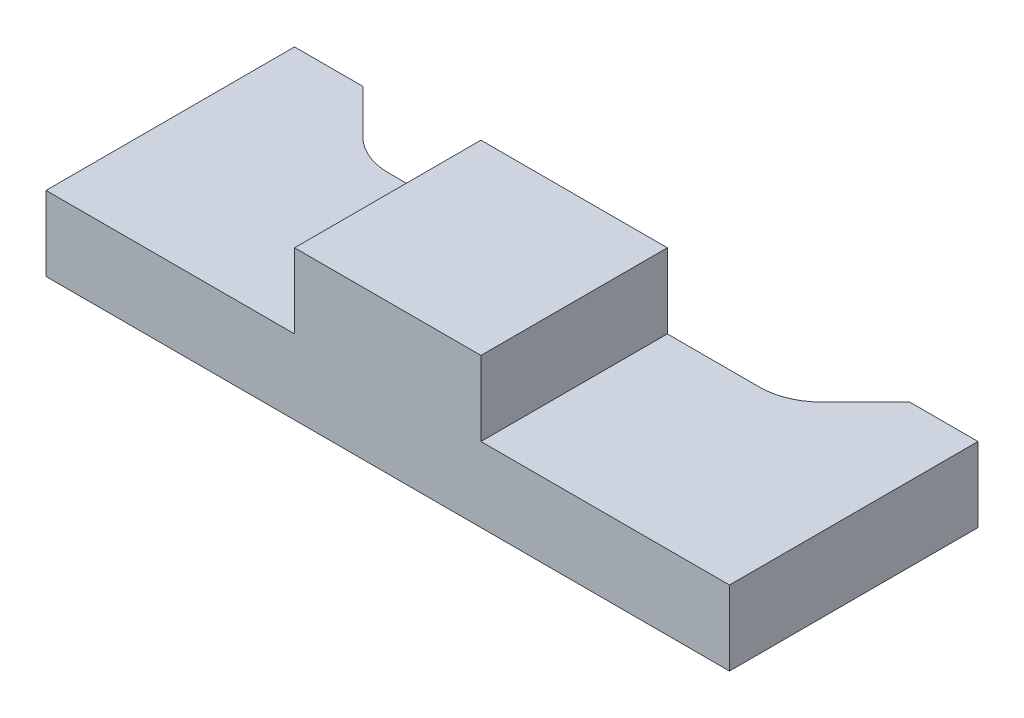
SolidWorks part; units mm, degrees
material "1060 Alloy"
ref_plane "Front Plane" through (0, 0, 0) normal (0, 0, 1) x (1, 0, 0)
ref_plane "Top Plane" through (0, 0, 0) normal (0, 1, 0) x (1, 0, 0)
ref_plane "Right Plane" through (0, 0, 0) normal (1, 0, 0) x (0, 0, -1)
sketch "Sketch4" plane through (0, 0, 0) normal (0, 0, 1) x (1, 0, 0)
  line L0 (-27.5, 0) -> (27.5, 0)
  line L1 (27.5, 0) -> (27.5, 6)
  line L2 (27.5, 6) -> (7.5, 6)
  line L3 (7.5, 6) -> (7.5, 12)
  line L4 (7.5, 12) -> (-7.5, 12)
  line L5 (-7.5, 12) -> (-7.5, 6)
  line L6 (-7.5, 6) -> (-27.5, 6)
  line L7 (-27.5, 6) -> (-27.5, 0)
  dimension "D1" = 6
  dimension "D2" = 55
  dimension "D3" = 15
  dimension "D4" = 12
extrude "Boss-Extrude2" add sketch "Sketch4" along normal blind 20
hole_wizard "Tap Drill for M6 Tap2" positions "Sketch6" profile "Sketch5" hole size "M6" standard "ISO"
sketch "Sketch6" plane through (0, 0, 0) normal (0, 0, -1) x (-1, 0, 0)
  line L0 (-7.5, 12) -> (7.5, 12) construction
  point P0 (0, 6)
  dimension "D1" = 6
sketch "Sketch5" plane through (0, 6, 0) normal (1, 0, 0) x (0, 1, 0)
  line L0 (0, 0) -> (0, 9.5022)
  line L1 (0, 9.5022) -> (2.5, 8)
  line L2 (2.5, 8) -> (2.5, 0)
  line L5 (2.5, 0) -> (0, 0)
  line L10 (0, 9.5022) -> (-2.5, 8) construction
  line L11 (0, -6.35) -> (0, 107.95) construction
  dimension "Hole Dia." = 5
  dimension "Hole Depth" = 8
  dimension "Drill Angle" = 118
sketch "Sketch7" plane through (0, 12, 0) normal (0, 1, 0) x (1, 0, 0)
  line L0 (-7.5, 0) -> (-27.5, 0) construction
  line L1 (-22, 0) -> (22, 0)
  line L2 (-22, 0) -> (-17, -5)
  line L3 (-17, -5) -> (17, -5)
  line L4 (22, 0) -> (17, -5)
  line L5 (27.5, 0) -> (7.5, 0) construction
  dimension "D1" = 45
  dimension "D2" = 45
  dimension "D3" = 34
  dimension "D4" = 17
  dimension "D5" = 5
extrude "Cut-Extrude1" cut sketch "Sketch7" against normal up to next
fillet "Fillet1" radius 5 2 edges at (-17, 3, 5) (17, 3, 5)
